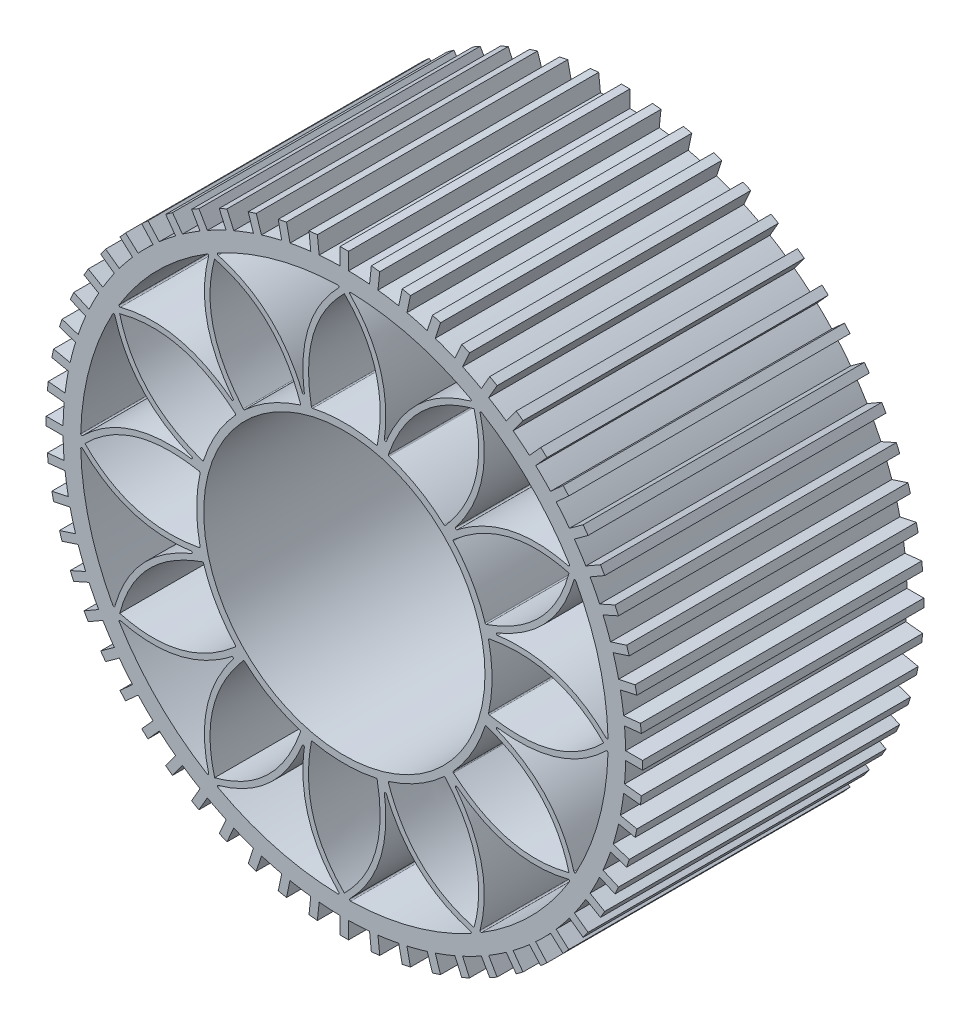
SolidWorks part; units mm, degrees
ref_plane "Front Plane" through (0, 0, 0) normal (0, 0, 1) x (1, 0, 0)
ref_plane "Top Plane" through (0, 0, 0) normal (0, 1, 0) x (1, 0, 0)
ref_plane "Right Plane" through (0, 0, 0) normal (1, 0, 0) x (0, 0, -1)
sketch "Sketch1" plane through (0, 0, 0) normal (0, 0, 1) x (1, 0, 0)
  line L0 (0, 53.34) -> (0, 96.52) construction
  line L8 (-6.9623, 52.8837) -> (-10.8078, 82.0937)
  line L9 (0, 96.52) -> (0, 101.6) construction
  line L10 (-13.8054, 51.5225) -> (-16.6979, 62.3175)
  line L11 (0, 101.6) -> (0, 107.696)
  line L12 (-1.524, 107.696) -> (1.524, 107.696)
  line L13 (-1.524, 107.696) -> (-1.524, 101.5886)
  line L14 (1.524, 107.696) -> (1.524, 101.5886)
  line L15 (12.7729, 106.9467) -> (12.1345, 100.8728)
  line L16 (9.7416, 107.2653) -> (9.1032, 101.1914)
  line L17 (9.7416, 107.2653) -> (12.7729, 106.9467)
  line L18 (23.882, 105.0257) -> (22.6121, 99.0518)
  line L19 (20.9006, 105.6594) -> (19.6308, 99.6855)
  line L20 (20.9006, 105.6594) -> (23.882, 105.0257)
  line L21 (34.7293, 101.954) -> (32.842, 96.1455)
  line L22 (31.8305, 102.8959) -> (29.9432, 97.0874)
  line L23 (31.8305, 102.8959) -> (34.7293, 101.954)
  line L24 (45.1962, 97.7653) -> (42.712, 92.1859)
  line L25 (42.4117, 99.0051) -> (39.9276, 93.4256)
  line L26 (42.4117, 99.0051) -> (45.1962, 97.7653)
  line L27 (55.1678, 92.5055) -> (52.1141, 87.2163)
  line L28 (52.5282, 94.0295) -> (49.4745, 88.7403)
  line L29 (52.5282, 94.0295) -> (55.1678, 92.5055)
  line L30 (64.5351, 86.2321) -> (60.9452, 81.2911)
  line L31 (62.0692, 88.0237) -> (58.4793, 83.0827)
  line L32 (62.0692, 88.0237) -> (64.5351, 86.2321)
  line L33 (73.1952, 79.014) -> (69.1086, 74.4753)
  line L34 (70.9301, 81.0535) -> (66.8435, 76.5148)
  line L35 (70.9301, 81.0535) -> (73.1952, 79.014)
  line L36 (81.0535, 70.9301) -> (76.5148, 66.8435)
  line L37 (79.014, 73.1952) -> (74.4753, 69.1086)
  line L38 (79.014, 73.1952) -> (81.0535, 70.9301)
  line L39 (88.0237, 62.0692) -> (83.0827, 58.4793)
  line L40 (86.2321, 64.5351) -> (81.2911, 60.9452)
  line L41 (86.2321, 64.5351) -> (88.0237, 62.0692)
  line L42 (94.0295, 52.5282) -> (88.7403, 49.4745)
  line L43 (92.5055, 55.1678) -> (87.2163, 52.1141)
  line L44 (92.5055, 55.1678) -> (94.0295, 52.5282)
  line L45 (99.0051, 42.4117) -> (93.4256, 39.9276)
  line L46 (97.7653, 45.1962) -> (92.1859, 42.712)
  line L47 (97.7653, 45.1962) -> (99.0051, 42.4117)
  line L48 (102.8959, 31.8305) -> (97.0874, 29.9432)
  line L49 (101.954, 34.7293) -> (96.1455, 32.842)
  line L50 (101.954, 34.7293) -> (102.8959, 31.8305)
  line L51 (105.6594, 20.9006) -> (99.6855, 19.6308)
  line L52 (105.0257, 23.882) -> (99.0518, 22.6121)
  line L53 (105.0257, 23.882) -> (105.6594, 20.9006)
  line L54 (107.2653, 9.7416) -> (101.1914, 9.1032)
  line L55 (106.9467, 12.7729) -> (100.8728, 12.1345)
  line L56 (106.9467, 12.7729) -> (107.2653, 9.7416)
  line L57 (107.696, -1.524) -> (101.5886, -1.524)
  line L58 (107.696, 1.524) -> (101.5886, 1.524)
  line L59 (107.696, 1.524) -> (107.696, -1.524)
  line L60 (106.9467, -12.7729) -> (100.8728, -12.1345)
  line L61 (107.2653, -9.7416) -> (101.1914, -9.1032)
  line L62 (107.2653, -9.7416) -> (106.9467, -12.7729)
  line L63 (105.0257, -23.882) -> (99.0518, -22.6121)
  line L64 (105.6594, -20.9006) -> (99.6855, -19.6308)
  line L65 (105.6594, -20.9006) -> (105.0257, -23.882)
  line L66 (101.954, -34.7293) -> (96.1455, -32.842)
  line L67 (102.8959, -31.8305) -> (97.0874, -29.9432)
  line L68 (102.8959, -31.8305) -> (101.954, -34.7293)
  line L69 (97.7653, -45.1962) -> (92.1859, -42.712)
  line L70 (99.0051, -42.4117) -> (93.4256, -39.9276)
  line L71 (99.0051, -42.4117) -> (97.7653, -45.1962)
  line L72 (92.5055, -55.1678) -> (87.2163, -52.1141)
  line L73 (94.0295, -52.5282) -> (88.7403, -49.4745)
  line L74 (94.0295, -52.5282) -> (92.5055, -55.1678)
  line L75 (86.2321, -64.5351) -> (81.2911, -60.9452)
  line L76 (88.0237, -62.0692) -> (83.0827, -58.4793)
  line L77 (88.0237, -62.0692) -> (86.2321, -64.5351)
  line L78 (79.014, -73.1952) -> (74.4753, -69.1086)
  line L79 (81.0535, -70.9301) -> (76.5148, -66.8435)
  line L80 (81.0535, -70.9301) -> (79.014, -73.1952)
  line L81 (70.9301, -81.0535) -> (66.8435, -76.5148)
  line L82 (73.1952, -79.014) -> (69.1086, -74.4753)
  line L83 (73.1952, -79.014) -> (70.9301, -81.0535)
  line L84 (62.0692, -88.0237) -> (58.4793, -83.0827)
  line L85 (64.5351, -86.2321) -> (60.9452, -81.2911)
  line L86 (64.5351, -86.2321) -> (62.0692, -88.0237)
  line L87 (52.5282, -94.0295) -> (49.4745, -88.7403)
  line L88 (55.1678, -92.5055) -> (52.1141, -87.2163)
  line L89 (55.1678, -92.5055) -> (52.5282, -94.0295)
  line L90 (42.4117, -99.0051) -> (39.9276, -93.4256)
  line L91 (45.1962, -97.7653) -> (42.712, -92.1859)
  line L92 (45.1962, -97.7653) -> (42.4117, -99.0051)
  line L93 (31.8305, -102.8959) -> (29.9432, -97.0874)
  line L94 (34.7293, -101.954) -> (32.842, -96.1455)
  line L95 (34.7293, -101.954) -> (31.8305, -102.8959)
  line L96 (20.9006, -105.6594) -> (19.6308, -99.6855)
  line L97 (23.882, -105.0257) -> (22.6121, -99.0518)
  line L98 (23.882, -105.0257) -> (20.9006, -105.6594)
  line L99 (9.7416, -107.2653) -> (9.1032, -101.1914)
  line L100 (12.7729, -106.9467) -> (12.1345, -100.8728)
  line L101 (12.7729, -106.9467) -> (9.7416, -107.2653)
  line L102 (-1.524, -107.696) -> (-1.524, -101.5886)
  line L103 (1.524, -107.696) -> (1.524, -101.5886)
  line L104 (1.524, -107.696) -> (-1.524, -107.696)
  line L105 (-12.7729, -106.9467) -> (-12.1345, -100.8728)
  line L106 (-9.7416, -107.2653) -> (-9.1032, -101.1914)
  line L107 (-9.7416, -107.2653) -> (-12.7729, -106.9467)
  line L108 (-23.882, -105.0257) -> (-22.6121, -99.0518)
  line L109 (-20.9006, -105.6594) -> (-19.6308, -99.6855)
  line L110 (-20.9006, -105.6594) -> (-23.882, -105.0257)
  line L111 (-34.7293, -101.954) -> (-32.842, -96.1455)
  line L112 (-31.8305, -102.8959) -> (-29.9432, -97.0874)
  line L113 (-31.8305, -102.8959) -> (-34.7293, -101.954)
  line L114 (-45.1962, -97.7653) -> (-42.712, -92.1859)
  line L115 (-42.4117, -99.0051) -> (-39.9276, -93.4256)
  line L116 (-42.4117, -99.0051) -> (-45.1962, -97.7653)
  line L117 (-55.1678, -92.5055) -> (-52.1141, -87.2163)
  line L118 (-52.5282, -94.0295) -> (-49.4745, -88.7403)
  line L119 (-52.5282, -94.0295) -> (-55.1678, -92.5055)
  line L120 (-64.5351, -86.2321) -> (-60.9452, -81.2911)
  line L121 (-62.0692, -88.0237) -> (-58.4793, -83.0827)
  line L122 (-62.0692, -88.0237) -> (-64.5351, -86.2321)
  line L123 (-73.1952, -79.014) -> (-69.1086, -74.4753)
  line L124 (-70.9301, -81.0535) -> (-66.8435, -76.5148)
  line L125 (-70.9301, -81.0535) -> (-73.1952, -79.014)
  line L126 (-81.0535, -70.9301) -> (-76.5148, -66.8435)
  line L127 (-79.014, -73.1952) -> (-74.4753, -69.1086)
  line L128 (-79.014, -73.1952) -> (-81.0535, -70.9301)
  line L129 (-88.0237, -62.0692) -> (-83.0827, -58.4793)
  line L130 (-86.2321, -64.5351) -> (-81.2911, -60.9452)
  line L131 (-86.2321, -64.5351) -> (-88.0237, -62.0692)
  line L132 (-94.0295, -52.5282) -> (-88.7403, -49.4745)
  line L133 (-92.5055, -55.1678) -> (-87.2163, -52.1141)
  line L134 (-92.5055, -55.1678) -> (-94.0295, -52.5282)
  line L135 (-99.0051, -42.4117) -> (-93.4256, -39.9276)
  line L136 (-97.7653, -45.1962) -> (-92.1859, -42.712)
  line L137 (-97.7653, -45.1962) -> (-99.0051, -42.4117)
  line L138 (-102.8959, -31.8305) -> (-97.0874, -29.9432)
  line L139 (-101.954, -34.7293) -> (-96.1455, -32.842)
  line L140 (-101.954, -34.7293) -> (-102.8959, -31.8305)
  line L141 (-105.6594, -20.9006) -> (-99.6855, -19.6308)
  line L142 (-105.0257, -23.882) -> (-99.0518, -22.6121)
  line L143 (-105.0257, -23.882) -> (-105.6594, -20.9006)
  line L144 (-107.2653, -9.7416) -> (-101.1914, -9.1032)
  line L145 (-106.9467, -12.7729) -> (-100.8728, -12.1345)
  line L146 (-106.9467, -12.7729) -> (-107.2653, -9.7416)
  line L147 (-107.696, 1.524) -> (-101.5886, 1.524)
  line L148 (-107.696, -1.524) -> (-101.5886, -1.524)
  line L149 (-107.696, -1.524) -> (-107.696, 1.524)
  line L150 (-106.9467, 12.7729) -> (-100.8728, 12.1345)
  line L151 (-107.2653, 9.7416) -> (-101.1914, 9.1032)
  line L152 (-107.2653, 9.7416) -> (-106.9467, 12.7729)
  line L153 (-105.0257, 23.882) -> (-99.0518, 22.6121)
  line L154 (-105.6594, 20.9006) -> (-99.6855, 19.6308)
  line L155 (-105.6594, 20.9006) -> (-105.0257, 23.882)
  line L156 (-101.954, 34.7293) -> (-96.1455, 32.842)
  line L157 (-102.8959, 31.8305) -> (-97.0874, 29.9432)
  line L158 (-102.8959, 31.8305) -> (-101.954, 34.7293)
  line L159 (-97.7653, 45.1962) -> (-92.1859, 42.712)
  line L160 (-99.0051, 42.4117) -> (-93.4256, 39.9276)
  line L161 (-99.0051, 42.4117) -> (-97.7653, 45.1962)
  line L162 (-92.5055, 55.1678) -> (-87.2163, 52.1141)
  line L163 (-94.0295, 52.5282) -> (-88.7403, 49.4745)
  line L164 (-94.0295, 52.5282) -> (-92.5055, 55.1678)
  line L165 (-86.2321, 64.5351) -> (-81.2911, 60.9452)
  line L166 (-88.0237, 62.0692) -> (-83.0827, 58.4793)
  line L167 (-88.0237, 62.0692) -> (-86.2321, 64.5351)
  line L168 (-79.014, 73.1952) -> (-74.4753, 69.1086)
  line L169 (-81.0535, 70.9301) -> (-76.5148, 66.8435)
  line L170 (-81.0535, 70.9301) -> (-79.014, 73.1952)
  line L171 (-70.9301, 81.0535) -> (-66.8435, 76.5148)
  line L172 (-73.1952, 79.014) -> (-69.1086, 74.4753)
  line L173 (-73.1952, 79.014) -> (-70.9301, 81.0535)
  line L174 (-62.0692, 88.0237) -> (-58.4793, 83.0827)
  line L175 (-64.5351, 86.2321) -> (-60.9452, 81.2911)
  line L176 (-64.5351, 86.2321) -> (-62.0692, 88.0237)
  line L177 (-52.5282, 94.0295) -> (-49.4745, 88.7403)
  line L178 (-55.1678, 92.5055) -> (-52.1141, 87.2163)
  line L179 (-55.1678, 92.5055) -> (-52.5282, 94.0295)
  line L180 (-42.4117, 99.0051) -> (-39.9276, 93.4256)
  line L181 (-45.1962, 97.7653) -> (-42.712, 92.1859)
  line L182 (-45.1962, 97.7653) -> (-42.4117, 99.0051)
  line L183 (-31.8305, 102.8959) -> (-29.9432, 97.0874)
  line L184 (-34.7293, 101.954) -> (-32.842, 96.1455)
  line L185 (-34.7293, 101.954) -> (-31.8305, 102.8959)
  line L186 (-20.9006, 105.6594) -> (-19.6308, 99.6855)
  line L187 (-23.882, 105.0257) -> (-22.6121, 99.0518)
  line L188 (-23.882, 105.0257) -> (-20.9006, 105.6594)
  line L189 (-9.7416, 107.2653) -> (-9.1032, 101.1914)
  line L190 (-12.7729, 106.9467) -> (-12.1345, 100.8728)
  line L191 (-12.7729, 106.9467) -> (-9.7416, 107.2653)
  circle A0 centre (0, 0) radius 101.6
  circle A1 centre (0, 0) radius 96.52
  circle A2 centre (0, 0) radius 53.34
  circle A3 centre (0, 0) radius 95.25
  circle A4 centre (0, 0) radius 50.8
  spline S0 degree 1 poles (0, 96.52) (0, 53.34) knots 0 0 1 1 construction
  spline S1 degree 2 poles (0, 96.52) (-19.1372, 78.7716) (-13.8054, 51.5225) knots 0 0 0 1 1 1
  spline S2 degree 2 poles (0, 96.52) (19.1372, 78.7716) (13.8054, 51.5225) knots 0 0 0 1 1 1
  spline S3 degree 1 poles (0, 93.7029) (-11.8112, 51.9127) knots 0 0 1 1 construction
  spline S4 degree 1 poles (0, 93.7029) (11.8112, 51.9127) knots 0 0 1 1 construction
  spline S5 degree 2 poles (-11.8112, 51.9127) (-11.8184, 51.9497) (-11.8305, 52.0115) (-13.6573, 61.4983) (-11.6557, 75.1101) (-7.3712, 84.9577) (-2.1065, 91.6062) (0, 93.7029) knots 0.038396 0.038396 0.038396 0.039797 0.040731 0.398997 0.639398 0.879799 1 1 1 only from (-11.8305, 52.0115) to (0, 93.7029)
  spline S6 degree 2 poles (0, 93.7029) (2.1065, 91.6062) (7.3712, 84.9577) (11.6557, 75.1101) (13.6573, 61.4983) (11.8305, 52.0115) (11.8184, 51.9497) (11.8112, 51.9127) knots 0.038396 0.038396 0.038396 0.158596 0.398997 0.639398 0.997664 0.998599 1 1 1 only from (0, 93.7029) to (11.8305, 52.0115)
  spline S7 degree 2 poles (15.7602, 50.9585) (15.7643, 50.9704) (18.9216, 60.0878) (27.461, 70.8751) (36.0952, 77.2611) (43.9788, 80.3865) (46.8514, 81.1491) knots 0.040264 0.040264 0.040264 0.040731 0.398997 0.639398 0.879799 1 1 1
  spline S8 degree 2 poles (48.26, 83.5888) (22.8125, 77.7867) (13.8054, 51.5225) knots 0 0 0 1 1 1
  spline S9 degree 2 poles (46.8514, 81.1491) (47.6274, 78.28) (48.8625, 69.8899) (47.6492, 59.2194) (42.5767, 46.4304) (36.2595, 39.1375) (36.2512, 39.128) knots 0.038396 0.038396 0.038396 0.158596 0.398997 0.639398 0.997664 0.998132 0.998132 0.998132
  spline S10 degree 2 poles (48.26, 83.5888) (55.959, 58.6496) (37.7171, 37.7171) knots 0 0 0 1 1 1
  spline S11 degree 2 poles (39.128, 36.2512) (39.1375, 36.2595) (46.4304, 42.5767) (59.2194, 47.6492) (69.8899, 48.8625) (78.28, 47.6274) (81.1491, 46.8514) knots 0.040264 0.040264 0.040264 0.040731 0.398997 0.639398 0.879799 1 1 1
  spline S12 degree 2 poles (83.5888, 48.26) (58.6496, 55.959) (37.7171, 37.7171) knots 0 0 0 1 1 1
  spline S13 degree 2 poles (81.1491, 46.8514) (80.3865, 43.9788) (77.2611, 36.0952) (70.8751, 27.461) (60.0878, 18.9216) (50.9704, 15.7643) (50.9585, 15.7602) knots 0.038396 0.038396 0.038396 0.158596 0.398997 0.639398 0.997664 0.998132 0.998132 0.998132
  spline S14 degree 2 poles (83.5888, 48.26) (77.7867, 22.8125) (51.5225, 13.8054) knots 0 0 0 1 1 1
  spline S15 degree 2 poles (52.0115, 11.8305) (52.0238, 11.8329) (61.4983, 13.6573) (75.1101, 11.6557) (84.9577, 7.3712) (91.6062, 2.1065) (93.7029, 0) knots 0.040264 0.040264 0.040264 0.040731 0.398997 0.639398 0.879799 1 1 1
  spline S16 degree 2 poles (96.52, 0) (78.7716, 19.1372) (51.5225, 13.8054) knots 0 0 0 1 1 1
  spline S17 degree 2 poles (93.7029, 0) (91.6062, -2.1065) (84.9577, -7.3712) (75.1101, -11.6557) (61.4983, -13.6573) (52.0238, -11.8329) (52.0115, -11.8305) knots 0.038396 0.038396 0.038396 0.158596 0.398997 0.639398 0.997664 0.998132 0.998132 0.998132
  spline S18 degree 2 poles (96.52, 0) (78.7716, -19.1372) (51.5225, -13.8054) knots 0 0 0 1 1 1
  spline S19 degree 2 poles (50.9585, -15.7602) (50.9704, -15.7643) (60.0878, -18.9216) (70.8751, -27.461) (77.2611, -36.0952) (80.3865, -43.9788) (81.1491, -46.8514) knots 0.040264 0.040264 0.040264 0.040731 0.398997 0.639398 0.879799 1 1 1
  spline S20 degree 2 poles (83.5888, -48.26) (77.7867, -22.8125) (51.5225, -13.8054) knots 0 0 0 1 1 1
  spline S21 degree 2 poles (81.1491, -46.8514) (78.28, -47.6274) (69.8899, -48.8625) (59.2194, -47.6492) (46.4304, -42.5767) (39.1375, -36.2595) (39.128, -36.2512) knots 0.038396 0.038396 0.038396 0.158596 0.398997 0.639398 0.997664 0.998132 0.998132 0.998132
  spline S22 degree 2 poles (83.5888, -48.26) (58.6496, -55.959) (37.7171, -37.7171) knots 0 0 0 1 1 1
  spline S23 degree 2 poles (36.2512, -39.128) (36.2595, -39.1375) (42.5767, -46.4304) (47.6492, -59.2194) (48.8625, -69.8899) (47.6274, -78.28) (46.8514, -81.1491) knots 0.040264 0.040264 0.040264 0.040731 0.398997 0.639398 0.879799 1 1 1
  spline S24 degree 2 poles (48.26, -83.5888) (55.959, -58.6496) (37.7171, -37.7171) knots 0 0 0 1 1 1
  spline S25 degree 2 poles (46.8514, -81.1491) (43.9788, -80.3865) (36.0952, -77.2611) (27.461, -70.8751) (18.9216, -60.0878) (15.7643, -50.9704) (15.7602, -50.9585) knots 0.038396 0.038396 0.038396 0.158596 0.398997 0.639398 0.997664 0.998132 0.998132 0.998132
  spline S26 degree 2 poles (48.26, -83.5888) (22.8125, -77.7867) (13.8054, -51.5225) knots 0 0 0 1 1 1
  spline S27 degree 2 poles (11.7936, -52.0199) (11.8, -52.0527) (11.8112, -52.1103) (13.6381, -61.5971) (11.6364, -75.2089) (7.352, -85.0565) (2.0872, -91.705) (-0.0193, -93.8017) knots 0.038554 0.038554 0.038554 0.039797 0.040731 0.398997 0.639398 0.879799 1 1 1
  spline S28 degree 2 poles (0, -96.52) (19.1372, -78.7716) (13.8054, -51.5225) knots 0 0 0 1 1 1
  spline S29 degree 2 poles (-0.0193, -93.8017) (-2.1257, -91.705) (-7.3905, -85.0565) (-11.6749, -75.2089) (-13.6766, -61.5971) (-11.8498, -52.1103) (-11.8377, -52.0485) (-11.8305, -52.0115) knots 0.038396 0.038396 0.038396 0.158596 0.398997 0.639398 0.997664 0.998599 1 1 1
  spline S30 degree 2 poles (0, -96.52) (-19.1372, -78.7716) (-13.8054, -51.5225) knots 0 0 0 1 1 1
  spline S31 degree 2 poles (-15.7215, -50.9705) (-15.7292, -50.9927) (-18.8995, -60.117) (-27.4502, -70.8954) (-36.0911, -77.2724) (-43.978, -80.3895) (-46.8514, -81.1491) knots 0.039859 0.039859 0.039859 0.040731 0.398997 0.639398 0.879799 1 1 1
  spline S32 degree 2 poles (-48.26, -83.5888) (-22.8125, -77.7867) (-13.8054, -51.5225) knots 0 0 0 1 1 1
  spline S33 degree 2 poles (-46.8514, -81.1491) (-47.6304, -78.2809) (-48.8743, -69.892) (-47.6721, -59.2203) (-42.6131, -46.426) (-36.2964, -39.1182) (-36.281, -39.1005) knots 0.038396 0.038396 0.038396 0.158596 0.398997 0.639398 0.997664 0.998537 0.998537 0.998537
  spline S34 degree 2 poles (-48.26, -83.5888) (-55.959, -58.6496) (-37.7171, -37.7171) knots 0 0 0 1 1 1
  spline S35 degree 2 poles (-39.1005, -36.281) (-39.1182, -36.2964) (-46.426, -42.6131) (-59.2203, -47.6721) (-69.892, -48.8743) (-78.2809, -47.6304) (-81.1491, -46.8514) knots 0.039859 0.039859 0.039859 0.040731 0.398997 0.639398 0.879799 1 1 1
  spline S36 degree 2 poles (-83.5888, -48.26) (-58.6496, -55.959) (-37.7171, -37.7171) knots 0 0 0 1 1 1
  spline S37 degree 2 poles (-81.1491, -46.8514) (-80.3895, -43.978) (-77.2724, -36.0911) (-70.8954, -27.4502) (-60.117, -18.8995) (-50.9927, -15.7292) (-50.9705, -15.7215) knots 0.038396 0.038396 0.038396 0.158596 0.398997 0.639398 0.997664 0.998537 0.998537 0.998537
  spline S38 degree 2 poles (-83.5888, -48.26) (-77.7867, -22.8125) (-51.5225, -13.8054) knots 0 0 0 1 1 1
  spline S39 degree 2 poles (-52.0025, -11.87) (-52.0256, -11.8745) (-61.5126, -13.6911) (-75.1223, -11.6751) (-84.9654, -7.3804) (-91.6084, -2.1087) (-93.7029, 0) knots 0.039859 0.039859 0.039859 0.040731 0.398997 0.639398 0.879799 1 1 1
  spline S40 degree 2 poles (-96.52, 0) (-78.7716, -19.1372) (-51.5225, -13.8054) knots 0 0 0 1 1 1
  spline S41 degree 2 poles (-93.7029, 0) (-91.6084, 2.1087) (-84.9654, 7.3804) (-75.1223, 11.6751) (-61.5126, 13.6911) (-52.0256, 11.8745) (-52.0025, 11.87) knots 0.038396 0.038396 0.038396 0.158596 0.398997 0.639398 0.997664 0.998537 0.998537 0.998537
  spline S42 degree 2 poles (-96.52, 0) (-78.7716, 19.1372) (-51.5225, 13.8054) knots 0 0 0 1 1 1
  spline S43 degree 2 poles (-50.9705, 15.7215) (-50.9927, 15.7292) (-60.117, 18.8995) (-70.8954, 27.4502) (-77.2724, 36.0911) (-80.3895, 43.978) (-81.1491, 46.8514) knots 0.039859 0.039859 0.039859 0.040731 0.398997 0.639398 0.879799 1 1 1
  spline S44 degree 2 poles (-83.5888, 48.26) (-77.7867, 22.8125) (-51.5225, 13.8054) knots 0 0 0 1 1 1
  spline S45 degree 2 poles (-81.1491, 46.8514) (-78.2809, 47.6304) (-69.892, 48.8743) (-59.2203, 47.6721) (-46.426, 42.6131) (-39.1182, 36.2964) (-39.1005, 36.281) knots 0.038396 0.038396 0.038396 0.158596 0.398997 0.639398 0.997664 0.998537 0.998537 0.998537
  spline S46 degree 2 poles (-83.5888, 48.26) (-58.6496, 55.959) (-37.7171, 37.7171) knots 0 0 0 1 1 1
  spline S47 degree 2 poles (-36.281, 39.1005) (-36.2964, 39.1182) (-42.6131, 46.426) (-47.6721, 59.2203) (-48.8743, 69.892) (-47.6304, 78.2809) (-46.8514, 81.1491) knots 0.039859 0.039859 0.039859 0.040731 0.398997 0.639398 0.879799 1 1 1
  spline S48 degree 2 poles (-48.26, 83.5888) (-55.959, 58.6496) (-37.7171, 37.7171) knots 0 0 0 1 1 1
  spline S49 degree 2 poles (-46.8514, 81.1491) (-43.978, 80.3895) (-36.0911, 77.2724) (-27.4502, 70.8954) (-18.8995, 60.117) (-15.7286, 50.9911) (-15.7081, 50.9316) (-15.6958, 50.8959) knots 0.038396 0.038396 0.038396 0.158596 0.398997 0.639398 0.997664 0.998599 1 1 1
  spline S50 degree 2 poles (-48.26, 83.5888) (-22.8125, 77.7867) (-13.8054, 51.5225) knots 0 0 0 1 1 1
  point P24 (0.3837, 0.1173)
  point P61 (0, 107.696)
  point P92 (0, 0)
  point P330 (0, 0)
  point P359 (0, 0)
  dimension "D1" = 203.2
  dimension "D2" = 193.04
  dimension "D3" = 106.68
  dimension "D12" = 190.5
  dimension "D10" = 0
  dimension "D5" = 7.5
  dimension "D6" = 6.096
  dimension "D7" = 3.048
  dimension "D8" = 29.21
  dimension "D9" = 60
  dimension "D11" = 2.032
  dimension "D14" = 0
  dimension "D15" = 15
  dimension "D13" = 2.54
extrude "Boss-Extrude1" add sketch "Sketch1" along normal blind 101.6 contours A2 | S5 S6 A2 S2 A3 S1 L8 | S10 A3 S8 A2 S7 S9 | A2 S5 L8 S1 | S14 A3 S12 A2 S11 S13 | S26 A3 S24 A2 S23 S25 | S18 A3 S16 A2 S15 S17 | S20 A1 S18 A3 | A0 | S16 A1 S14 A3 | S18 S16 A3 | S46 A3 S44 A2 S43 S45 | A0 L162 L164 L163 | A0 L165 L167 L166 | S48 A1 S46 A3 | A0 L159 L161 L160 | S44 A1 S42 A3 | S46 S44 A3 | A0 L147 L149 L148 | A0 L153 L155 L154 | A0 L156 L158 L157 | S42 S40 A3 | S40 A1 S38 A3 | S42 A3 S40 A2 S39 S41 | A0 L150 L152 L151 | A0 L144 L146 L145 | A0 L108 L110 L109 | S32 A1 S30 A3 | A0 L102 L104 L103 | A0 L105 L107 L106 | A0 L111 L113 L112 | A0 L114 L116 L115 | A0 L117 L119 L118 | A0 L120 L122 L121 | A0 L123 L125 L124 | A0 L126 L128 L127 | A0 L129 L131 L130 | A0 L132 L134 L133 | A0 L135 L137 L136 | S38 A3 S36 A2 S35 S37 | S38 S36 A3 | S36 A1 S34 A3 | S34 A3 S32 A2 S31 S33 | S30 A3 S28 A2 S27 S29 | S30 S28 A3 | S28 A1 S26 A3 | S34 S32 A3 | A0 L138 L140 L139 | A0 L141 L143 L142 | A0 L99 L101 L100 | S22 A3 S20 A2 S19 S21 | A0 L81 L83 L82 | A0 L78 L80 L79 | A0 L84 L86 L85 | A0 L87 L89 L88 | A0 L90 L92 L91 | A0 L93 L95 L94 | A0 L96 L98 L97 | A0 L168 L170 L169 | A0 L171 L173 L172 | A0 L174 L176 L175 | A0 L177 L179 L178 | S50 A3 S48 A2 S47 S49 | S50 S48 A3 | A1 S50 A3 S1 | A0 L180 L182 L181 | A0 L183 L185 L184 | A0 L186 L188 L187 | A0 L15 L17 L16 | A0 L189 L191 L190 | S2 S1 A3 | S8 A1 S2 A3 | A0 L11 L12 L13 | A0 L14 L12 L11 | S10 S8 A3 | A0 L30 L32 L31 | A0 L27 L29 L28 | A0 L24 L26 L25 | A0 L21 L23 L22 | A0 L18 L20 L19 | A0 L33 L35 L34 | S12 A1 S10 A3 | A0 L36 L38 L37 | A0 L39 L41 L40 | A0 L42 L44 L43 | S14 S12 A3 | S26 S24 A3 | S24 A1 S22 A3 | A0 L75 L77 L76 | A0 L72 L74 L73 | A0 L69 L71 L70 | S22 S20 A3 | A0 L45 L47 L46 | A0 L48 L50 L49 | A0 L51 L53 L52 | A0 L54 L56 L55 | A0 L57 L59 L58 | A0 L60 L62 L61 | A0 L63 L65 L64 | A0 L66 L68 L67 | A4 region at (2.4029, 51.7756, 0) region at (-13.1418, 66.1175, 0) region at (-10.0434, 80.1763, 0) region at (26.3473, 71.3078, 0) region at (-14.9278, 51.8169, 0) region at (0, 95.6736, 0) region at (-24.7821, 92.4882, 0) region at (1.0193, 96.2474, 0) region at (47.8368, 82.8557, 0) region at (-47.8368, 82.8557, 0) region at (49.0053, 82.8427, 0) region at (-67.7052, 67.7052, 0) region at (58.4714, 48.5807, 0) region at (82.8557, 47.8368, 0) region at (92.7474, 24.8516, 0) region at (-38.8363, 37.4108, 0) region at (-82.8557, 47.8368, 0) region at (-83.8623, 47.241, 0) region at (95.6736, 0, 0) region at (92.7474, -24.8516, 0) region at (-96.2474, -1.0193, 0) region at (-95.6736, 0, 0) region at (94.7178, 0.6639, 0) region at (82.8557, -47.8368, 0) region at (67.8967, -67.8967, 0) region at (-74.9423, 12.8889, 0) region at (-82.8427, -49.0053, 0) region at (-82.8557, -47.8368, 0) region at (47.8368, -82.8557, 0) region at (24.8516, -92.7474, 0) region at (81.9829, -47.3329, 0) region at (-47.241, -83.8623, 0) region at (-47.8368, -82.8557, 0) region at (-81.9829, -47.3329, 0) region at (0, -95.6736, 0) region at (47.3329, -81.9829, 0) region at (-47.3329, -81.9829, 0) region at (0, -94.7201, 0) region at (-0.7622, 104.6461, 0) region at (0.7622, 104.6461, 0) region at (0.7405, 98.7235, 0) region at (10.9385, 104.0728, 0) region at (-10.9385, 104.0728, 0) region at (21.7571, 102.3593, 0) region at (-21.7571, 102.3593, 0) region at (32.3374, 99.5243, 0) region at (-32.3374, 99.5243, 0) region at (42.5634, 95.599, 0) region at (-42.5634, 95.599, 0) region at (52.323, 90.6262, 0) region at (-52.323, 90.6262, 0) region at (61.5094, 84.6605, 0) region at (-61.5094, 84.6605, 0) region at (70.0219, 77.7672, 0) region at (-70.0219, 77.7672, 0) region at (77.7672, 70.0219, 0) region at (-77.7672, 70.0219, 0) region at (84.6605, 61.5094, 0) region at (-84.6605, 61.5094, 0) region at (90.6262, 52.323, 0)
sketch "Sketch2" plane through (0, 0, 101.6) normal (0, 0, 1) x (1, 0, 0)
  circle A0 centre (0, 0) radius 50.8
  dimension "D1" = 101.6
extrude "Cut-Extrude1" cut sketch "Sketch2" against normal up to surface (101.6 mm away) contours A0 up to face at (0, 0, 0)
fillet "Fillet1" radius 0.381 60 edges at (-37.7171, 37.7171, 50.8) (-51.5225, 13.8054, 50.8) (-51.5225, -13.8054, 50.8) (-37.7171, -37.7171, 50.8) (-13.8054, 51.5225, 50.8) (13.8054, 51.5225, 50.8) (37.7171, 37.7171, 50.8) (51.5225, 13.8054, 50.8) (51.5225, -13.8054, 50.8) (37.7171, -37.7171, 50.8) (13.8054, -51.5225, 50.8) (-13.8054, -51.5225, 50.8) (39.128, 36.2512, 50.8) (15.7602, 50.9585, 50.8) (-11.8305, 52.0115, 50.8) (-36.281, 39.1005, 50.8) (-50.9705, 15.7215, 50.8) (-52.0025, -11.87, 50.8) (-39.1005, -36.281, 50.8) (-15.7215, -50.9705, 50.8) (11.7936, -52.0199, 50.8) (36.2512, -39.128, 50.8) (50.9585, -15.7602, 50.8) (52.0115, 11.8305, 50.8) (36.2512, 39.128, 50.8) (52.0115, -11.8305, 50.8) (50.9585, 15.7602, 50.8) (39.128, -36.2512, 50.8) (15.7602, -50.9585, 50.8) (-11.8305, -52.0115, 50.8) (-36.281, -39.1005, 50.8) (-50.9705, -15.7215, 50.8) (-52.0025, 11.87, 50.8) (-39.1005, 36.281, 50.8) (11.8305, 52.0115, 50.8) (-15.7215, 50.9705, 50.8) (-95.2406, 1.3352, 50.8) (-83.1484, -46.464, 50.8) (-48.7767, -81.8132, 50.8) (-1.3352, -95.2406, 50.8) (46.464, -83.1484, 50.8) (81.8132, -48.7767, 50.8) (95.2406, -1.3352, 50.8) (83.1484, 46.464, 50.8) (48.7767, 81.8132, 50.8) (1.3352, 95.2406, 50.8) (-46.464, 83.1484, 50.8) (-81.8132, 48.7767, 50.8) (-95.2406, -1.3352, 50.8) (-81.8132, -48.7767, 50.8) (-46.464, -83.1484, 50.8) (48.7767, -81.8132, 50.8) (1.3352, -95.2406, 50.8) (83.1484, -46.464, 50.8) (95.2406, 1.3352, 50.8) (81.8132, 48.7767, 50.8) (46.464, 83.1484, 50.8) (-1.3352, 95.2406, 50.8) (-48.7767, 81.8132, 50.8) (-83.1484, 46.464, 50.8)
